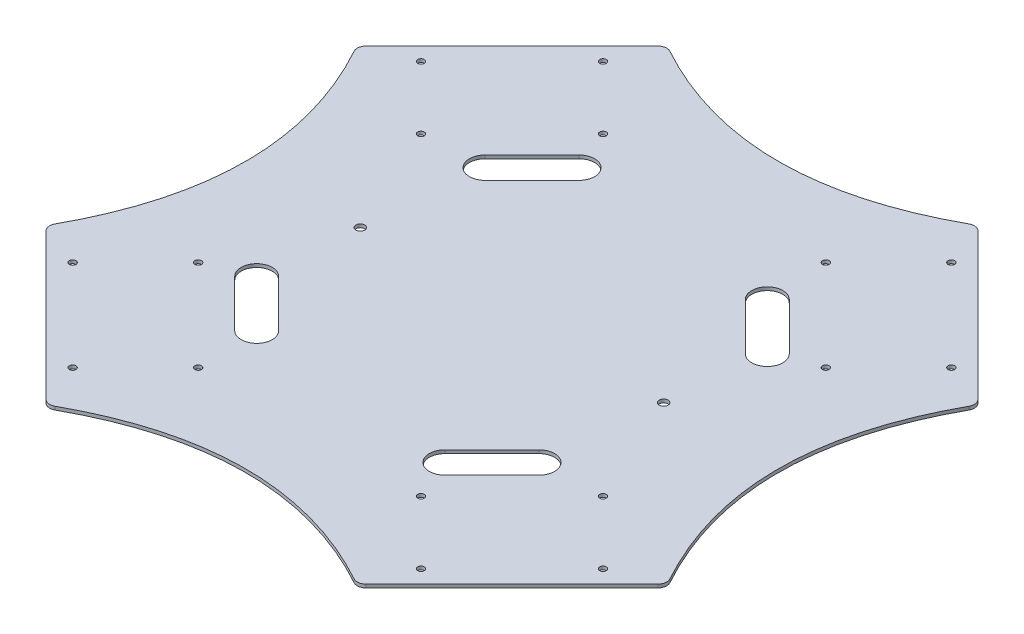
SolidWorks part; units mm, degrees
material "EM-CF"
ref_plane "Płaszczyzna przednia" through (0, 0, 0) normal (0, 0, 1) x (1, 0, 0)
ref_plane "Płaszczyzna górna" through (0, 0, 0) normal (0, 1, 0) x (1, 0, 0)
ref_plane "Płaszczyzna prawa" through (0, 0, 0) normal (1, 0, 0) x (0, 0, -1)
sketch "Szkic1" plane through (0, 0, 0) normal (0, 1, 0) x (1, 0, 0)
  line L0 (0, 0) -> (0, -120) construction
  line L1 (0, -120) -> (0, -140) construction
  line L2 (-70, -140) -> (70, -140) construction
  line L3 (0, 0) -> (-120, 0) construction
  line L4 (-120, 0) -> (-140, 0) construction
  line L5 (-140, 70) -> (-140, -70) construction
  line L6 (0, 0) -> (0, 120) construction
  line L7 (0, 120) -> (0, 140) construction
  line L8 (70, 140) -> (-70, 140) construction
  line L9 (0, 0) -> (120, 0) construction
  line L10 (120, 0) -> (140, 0) construction
  line L11 (140, -70) -> (140, 70) construction
  line L12 (-70, -140) -> (-140, -70)
  line L14 (70, -140) -> (140, -70)
  line L16 (140, 70) -> (70, 140)
  line L17 (-70, 140) -> (-140, 70)
  spline S0 degree 2 poles (-70, -140) (0, -100) (70, -140) knots 0 0 0 1 1 1
  spline S1 degree 2 poles (-140, 70) (-100, 0) (-140, -70) knots 0 0 0 1 1 1
  spline S2 degree 2 poles (70, 140) (0, 100) (-70, 140) knots 0 0 0 1 1 1
  spline S3 degree 2 poles (140, -70) (100, 0) (140, 70) knots 0 0 0 1 1 1
  point P7 (0, -140)
  point P14 (-140, 0)
  point P20 (0, 140)
  point P26 (140, 0)
  point P28 (0, 0)
  dimension "D1" = 120
  dimension "D2" = 20
  dimension "D3" = 140
extrude "Dodanie-wyciągnięcie1" add sketch "Szkic1" along normal blind 1.5
fillet "Zaokrąglenie1" radius 4 8 edges at (-140, 0.75, -70) (-70, 0.75, -140) (70, 0.75, -140) (140, 0.75, -70) (140, 0.75, 70) (70, 0.75, 140) (-140, 0.75, 70) (-70, 0.75, 140)
sketch "Szkic2" plane through (0, 1.5, 0) normal (0, 1, 0) x (1, 0, 0)
  line L0 (0, 0) -> (-70.7107, -70.7107) construction
  line L1 (-120.2082, -49.4975) -> (-49.4975, -120.2082) construction
  line L2 (-70.7107, -70.7107) -> (-98.9949, -98.9949) construction
  line L3 (-78.4889, -119.501) -> (-119.501, -78.4889) construction
  circle A0 centre (-78.4889, -119.501) radius 1.5
  circle A1 centre (-119.501, -78.4889) radius 1.5
  circle A2 centre (-50.2046, -91.2168) radius 1.5
  circle A3 centre (-91.2168, -50.2046) radius 1.5
  point P6 (-70.7107, -70.7107)
  point P10 (-98.9949, -98.9949)
  point P13 (-84.8528, -84.8528)
  point P16 (-84.8528, -84.8528)
  dimension "D5" = 3
  dimension "D1" = 100
  dimension "D3" = 40
extrude "Wytnij-wyciągnięcie1" cut sketch "Szkic2" against normal through all
ref_axis "Oś1" through (0, -82.2794, 0) along (0, 1, 0)
pattern_circular "Szyk kołowy1" count 4 every 90 about axis through (0, -82.2794, 0) along (0, 1, 0) of "Wytnij-wyciągnięcie1"
sketch "Szkic3" plane through (0, 1.5, 0) normal (0, 1, 0) x (1, 0, 0)
  line L0 (3.5562, 5.4754) -> (-53.0123, 62.0439) construction
  line L1 (-42.4057, 72.6505) -> (-63.6189, 51.4373)
  line L2 (-63.6189, 51.4373) -> (-42.4057, 72.6505) construction
  line L3 (-68.5687, 56.3871) -> (-47.3554, 77.6003)
  line L4 (-58.6692, 46.4876) -> (-37.456, 67.7008)
  arc A0 (-68.5687, 56.3871) -> (-58.6692, 46.4876) centre (-63.6189, 51.4373) ccw
  arc A1 (-37.456, 67.7008) -> (-47.3554, 77.6003) centre (-42.4057, 72.6505) ccw
  point P2 (-53.0123, 62.0439)
  point P5 (-53.0123, 62.0439)
  dimension "D1" = 80
  dimension "D2" = 30
  dimension "D3" = 14
extrude "Wytnij-wyciągnięcie2" cut sketch "Szkic3" against normal up to next contours L4 A1 L3 A0 region at (-57.6099, 1.5, -66.6416)
pattern_circular "Szyk kołowy2" count 4 every 90 about axis through (0, -82.2794, 0) along (0, 1, 0) of "Wytnij-wyciągnięcie2"
sketch "Szkic4" plane through (0, 1.5, 0) normal (0, 1, 0) x (1, 0, 0)
  line L0 (68.34, 0) -> (-68.34, 0) construction
  circle A0 centre (-68.34, 0) radius 2
  circle A1 centre (68.34, 0) radius 2
  point P3 (0, 0)
  dimension "D2" = 4
  dimension "D3" = 4
  dimension "D1" = 136.68
extrude "Wytnij-wyciągnięcie3" cut sketch "Szkic4" against normal up to next
equation "\"1.6.00mm\"=2"
